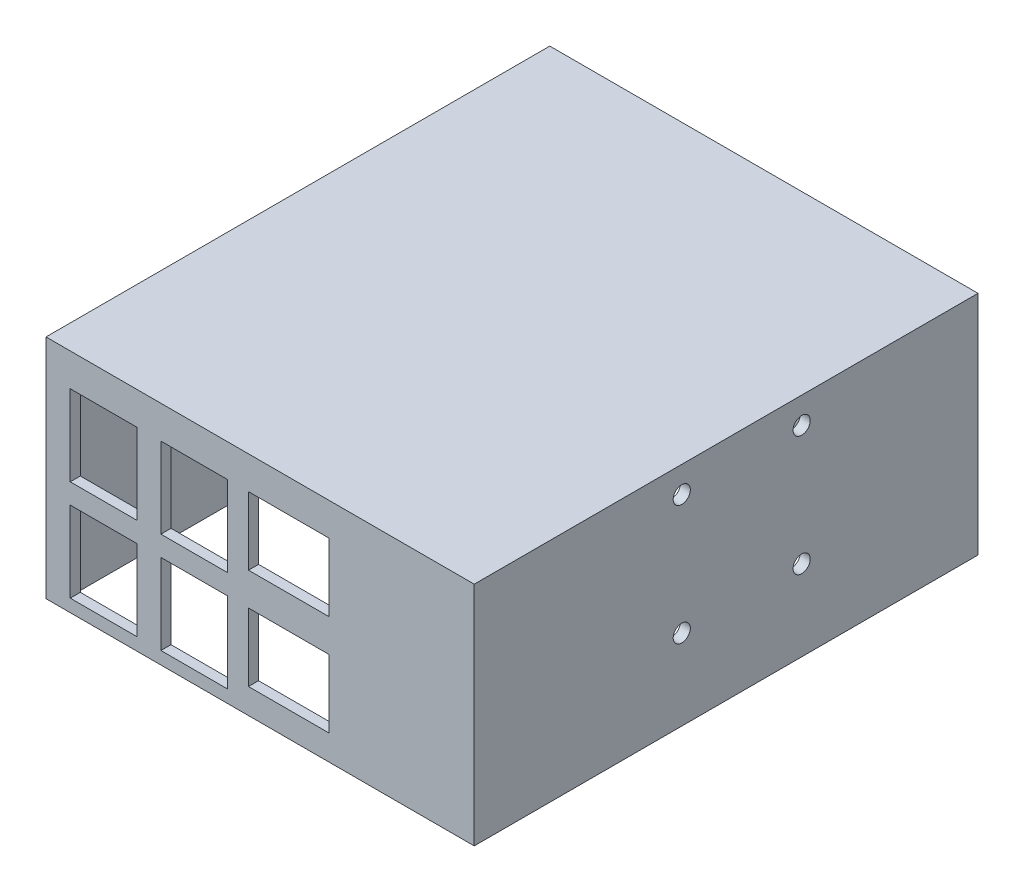
SolidWorks part; units mm, degrees
ref_plane "Front Plane" through (0, 0, 0) normal (0, 0, 1) x (1, 0, 0)
ref_plane "Top Plane" through (0, 0, 0) normal (0, 1, 0) x (1, 0, 0)
ref_plane "Right Plane" through (0, 0, 0) normal (1, 0, 0) x (0, 0, -1)
sketch "Sketch1" plane through (0, 0, 0) normal (0, 1, 0) x (1, 0, 0)
  line L1 (-42.5, -50) -> (42.5, -50)
  line L2 (-42.5, -50) -> (-42.5, 50)
  line L3 (-42.5, 50) -> (42.5, 50)
  line L4 (42.5, -50) -> (42.5, 50)
  line L5 (-42.5, -50) -> (42.5, 50) construction
  line L6 (-42.5, 50) -> (42.5, -50) construction
  point P0 (0, 0)
  dimension "D1" = 100
  dimension "D2" = 85
extrude "Boss-Extrude1" add sketch "Sketch1" along normal blind 45
shell "Shell1" thickness 2 removed face at (0, 0, 0)
sketch "Sketch3" plane through (0, 43, 0) normal (0, -1, 0) x (1, 0, 0)
  line L0 (-36.5, 24.5) -> (12.5, 24.5) construction
  line L1 (12.5, 24.5) -> (12.5, -33.5) construction
  line L2 (12.5, -33.5) -> (-36.5, -33.5) construction
  line L3 (-36.5, -33.5) -> (-36.5, 24.5) construction
  line L5 (-40.5, 48) -> (40.5, 48) construction
  line L6 (-36.5, -4.5) -> (-40.5, -4.5) construction
  line L7 (-40.5, -48) -> (-40.5, 48) construction
  line L8 (12.5, -4.5) -> (40.5, -4.5) construction
  line L9 (40.5, 48) -> (40.5, -48) construction
  circle A0 centre (-36.5, 24.5) radius 2.5
  circle A1 centre (12.5, 24.5) radius 2.5
  circle A2 centre (-36.5, -33.5) radius 2.5
  circle A3 centre (12.5, -33.5) radius 2.5
  dimension "D4" = 5
  dimension "D1" = 58
  dimension "D2" = 49
  dimension "D3" = 23.5
  dimension "D5" = 4
extrude "Boss-Extrude2" add sketch "Sketch3" along normal blind 3
sketch "Sketch4" plane through (0, 40, 0) normal (0, -1, 0) x (1, 0, 0)
  circle A0 centre (12.5, 24.5) radius 1.025
  circle A1 centre (-36.5, 24.5) radius 1.025
  circle A2 centre (-36.5, -33.5) radius 1.025
  circle A3 centre (12.5, -33.5) radius 1.025
  point P12 (0, 0)
  point P13 (0, 0)
  dimension "D1" = 2.05
extrude "Cut-Extrude1" cut sketch "Sketch4" against normal blind 2.7
sketch "Sketch17" plane through (0, 0, 50) normal (0, 0, 1) x (1, 0, 0)
  line L0 (0, 45) -> (0, 0) construction
  line L1 (-42.5, 45) -> (42.5, 45) construction
  line L2 (42.5, 38.5) -> (-42.5, 38.5) construction
  line L3 (-24.44, 22.5) -> (-37.69, 22.5)
  line L4 (-24.44, 22.5) -> (-24.44, 38.5)
  line L5 (-24.44, 38.5) -> (-37.69, 38.5)
  line L6 (-37.69, 22.5) -> (-37.69, 38.5)
  line L7 (-24.44, 22.5) -> (-37.69, 38.5) construction
  line L8 (-24.44, 38.5) -> (-37.69, 22.5) construction
  line L9 (-6.44, 22.5) -> (-19.69, 22.5)
  line L10 (-6.44, 22.5) -> (-6.44, 38.5)
  line L11 (-6.44, 38.5) -> (-19.69, 38.5)
  line L12 (-19.69, 22.5) -> (-19.69, 38.5)
  line L13 (-6.44, 22.5) -> (-19.69, 38.5) construction
  line L14 (-6.44, 38.5) -> (-19.69, 22.5) construction
  line L15 (13.69, 25) -> (-2.31, 25)
  line L16 (13.69, 25) -> (13.69, 38.5)
  line L17 (13.69, 38.5) -> (-2.31, 38.5)
  line L18 (-2.31, 25) -> (-2.31, 38.5)
  line L19 (13.69, 25) -> (-2.31, 38.5) construction
  line L20 (13.69, 38.5) -> (-2.31, 25) construction
  line L21 (42.5, 45) -> (42.5, 0) construction
  line L22 (-42.5, 45) -> (-42.5, 0) construction
  line L23 (13.69, 31.75) -> (42.5, 31.75) construction
  line L24 (-37.69, 30.5) -> (-42.5, 30.5) construction
  point P5 (-31.065, 30.5)
  point P10 (-13.065, 30.5)
  point P15 (5.69, 31.75)
  dimension "D1" = 6.5
  dimension "D2" = 13.5
  dimension "D3" = 16
  dimension "D4" = 16
  dimension "D5" = 13.25
  dimension "D6" = 4.75
  dimension "D7" = 4.13
  dimension "D8" = 4.81
extrude "Cut-Extrude2" cut sketch "Sketch17" against normal up to surface (2 mm away) up to face at (0, 21.5, 48)
pattern_linear "LPattern1" count 2 spacing 20 along (0, -1, 0) of "Cut-Extrude2"
sketch "Sketch18" plane through (42.5, 0, 0) normal (1, 0, 0) x (0, 0, -1)
  line L0 (15, 39.8) -> (-8.8, 39.8) construction
  line L1 (-2.85, 21.95) -> (0.125, 16)
  line L2 (-8.8, 39.8) -> (-8.8, 16) construction
  line L3 (-8.8, 16) -> (15, 16) construction
  line L4 (15, 16) -> (15, 39.8) construction
  line L5 (-50, 45) -> (50, 45) construction
  line L6 (50, 45) -> (50, 0) construction
  line L7 (3.1, 16) -> (3.1, 39.8) construction
  line L8 (3.1, 27.9) -> (-8.8, 27.9) construction
  line L9 (3.1, 27.9) -> (15, 27.9) construction
  line L10 (9.05, 27.9) -> (9.05, 16) construction
  line L11 (9.05, 21.95) -> (3.1, 21.95) construction
  line L12 (9.05, 21.95) -> (15, 21.95) construction
  line L13 (12.025, 16) -> (15, 21.95)
  line L14 (15, 21.95) -> (9.05, 21.95)
  line L15 (9.05, 21.95) -> (12.025, 16)
  line L22 (9.05, 21.95) -> (9.05, 16)
  line L23 (9.05, 16) -> (3.1, 18.975)
  line L24 (3.1, 18.975) -> (9.05, 21.95)
  line L25 (9.05, 21.95) -> (3.1, 21.95)
  line L26 (3.1, 21.95) -> (6.075, 27.9)
  line L27 (6.075, 27.9) -> (9.05, 21.95)
  line L28 (6.075, 21.95) -> (6.075, 27.9) construction
  line L29 (9.05, 18.975) -> (3.1, 18.975) construction
  line L30 (12.025, 16) -> (12.025, 21.95) construction
  line L31 (9.05, 21.95) -> (9.05, 27.9)
  line L32 (9.05, 27.9) -> (9.05, 21.95) construction
  line L33 (9.05, 27.9) -> (15, 24.925)
  line L34 (15, 24.925) -> (9.05, 21.95)
  line L35 (15, 24.925) -> (9.05, 24.925) construction
  line L36 (0.125, 16) -> (3.1, 21.95)
  line L37 (3.1, 21.95) -> (-2.85, 21.95)
  line L38 (0.125, 16) -> (0.125, 21.95) construction
  line L39 (-2.85, 18.975) -> (-8.8, 18.975) construction
  line L40 (-2.85, 21.95) -> (-2.85, 16)
  line L41 (-2.85, 16) -> (-8.8, 18.975)
  line L42 (-8.8, 18.975) -> (-2.85, 21.95)
  line L43 (-5.825, 21.95) -> (-5.825, 27.9) construction
  line L44 (-2.85, 21.95) -> (-8.8, 21.95)
  line L45 (-8.8, 21.95) -> (-5.825, 27.9)
  line L46 (-5.825, 27.9) -> (-2.85, 21.95)
  line L47 (3.1, 24.925) -> (-2.85, 24.925) construction
  line L48 (-2.85, 21.95) -> (-2.85, 27.9)
  line L49 (-2.85, 27.9) -> (3.1, 24.925)
  line L50 (3.1, 24.925) -> (-2.85, 21.95)
  line L51 (-2.85, 33.85) -> (0.125, 27.9)
  line L52 (0.125, 27.9) -> (3.1, 33.85)
  line L53 (3.1, 33.85) -> (-2.85, 33.85)
  line L54 (0.125, 27.9) -> (0.125, 33.85) construction
  line L55 (-2.85, 30.875) -> (-8.8, 30.875) construction
  line L56 (-2.85, 33.85) -> (-2.85, 27.9)
  line L57 (-2.85, 27.9) -> (-8.8, 30.875)
  line L58 (-8.8, 30.875) -> (-2.85, 33.85)
  line L59 (-5.825, 33.85) -> (-5.825, 39.8) construction
  line L60 (-2.85, 33.85) -> (-8.8, 33.85)
  line L61 (-8.8, 33.85) -> (-5.825, 39.8)
  line L62 (-5.825, 39.8) -> (-2.85, 33.85)
  line L63 (3.1, 36.825) -> (-2.85, 36.825) construction
  line L64 (-2.85, 33.85) -> (-2.85, 39.8)
  line L65 (-2.85, 39.8) -> (3.1, 36.825)
  line L66 (3.1, 36.825) -> (-2.85, 33.85)
  line L67 (9.05, 33.85) -> (12.025, 27.9)
  line L68 (12.025, 27.9) -> (15, 33.85)
  line L69 (15, 33.85) -> (9.05, 33.85)
  line L70 (12.025, 27.9) -> (12.025, 33.85) construction
  line L71 (9.05, 30.875) -> (3.1, 30.875) construction
  line L72 (9.05, 33.85) -> (9.05, 27.9)
  line L73 (9.05, 27.9) -> (3.1, 30.875)
  line L74 (3.1, 30.875) -> (9.05, 33.85)
  line L75 (6.075, 33.85) -> (6.075, 39.8) construction
  line L76 (9.05, 33.85) -> (3.1, 33.85)
  line L77 (3.1, 33.85) -> (6.075, 39.8)
  line L78 (6.075, 39.8) -> (9.05, 33.85)
  line L79 (15, 36.825) -> (9.05, 36.825) construction
  line L80 (9.05, 33.85) -> (9.05, 39.8)
  line L81 (9.05, 39.8) -> (15, 36.825)
  line L82 (15, 36.825) -> (9.05, 33.85)
  line L83 (-8.8, 21.95) -> (-8.8, 30.875)
  line L84 (-8.8, 30.875) -> (-8.8, 33.85)
  line L85 (-2.85, 39.8) -> (-5.825, 39.8)
  line L86 (-2.85, 39.8) -> (3.1, 39.8)
  line L87 (3.1, 39.8) -> (6.075, 39.8)
  line L88 (9.05, 39.8) -> (6.075, 39.8)
  line L89 (15, 36.825) -> (15, 33.85)
  line L90 (15, 27.9) -> (15, 33.85)
  line L91 (15, 21.95) -> (15, 27.9)
  line L92 (12.025, 16) -> (9.05, 16)
  line L93 (9.05, 16) -> (3.1, 16)
  line L94 (3.1, 16) -> (0.125, 16)
  line L95 (0.125, 16) -> (-2.85, 16)
  line L96 (-8.8, 21.95) -> (-8.8, 18.975)
  circle A0 centre (15, 39.8) radius 1.7
  circle A1 centre (-8.8, 39.8) radius 1.7
  circle A2 centre (-8.8, 16) radius 1.7
  circle A3 centre (15, 16) radius 1.7
  dimension "D1" = 3.4
  dimension "D2" = 23.8
  dimension "D3" = 5.2
  dimension "D4" = 35
  dimension "D5" = 2
  dimension "D6" = 2
extrude "Cut-Extrude3" cut sketch "Sketch18" against normal up to surface (2 mm away) contours A3 | A2 | A1 | A0 region at (42.5, 39.8, -15) region at (42.5, 39.8, 8.8) region at (42.5, 16, 8.8) region at (42.5, 16, -15) up to face at (40.5, 21.5, 0)
